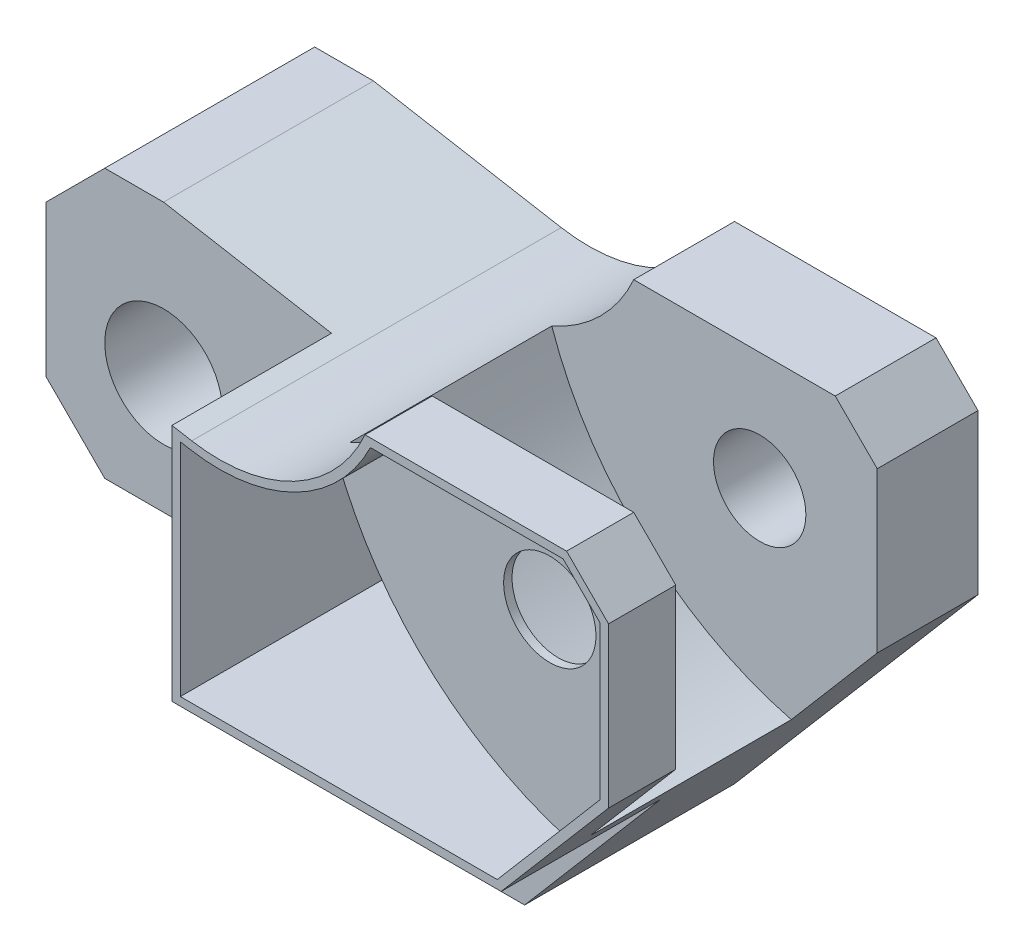
SolidWorks part; units mm, degrees
material "AISI 1020"
ref_plane "Plan de face" through (0, 0, 0) normal (0, 0, 1) x (1, 0, 0)
ref_plane "Plan de dessus" through (0, 0, 0) normal (0, 1, 0) x (1, 0, 0)
ref_plane "Plan de droite" through (0, 0, 0) normal (1, 0, 0) x (0, 0, -1)
sketch "Esquisse1" plane through (0, 0, 0) normal (0, 0, 1) x (1, 0, 0)
  line L0 (40.0103, -4.2308) -> (64.0103, -4.2308)
  line L1 (64.0103, -4.2308) -> (69.0103, -9.2308)
  line L2 (69.0103, -9.2308) -> (69.0103, -28.2308)
  line L3 (69.0103, -28.2308) -> (40.0103, -62.2308)
  line L4 (40.0103, -62.2308) -> (34.3073, -62.2308)
  line L6 (22.5858, -43.2308) -> (-9.9897, -43.2308)
  line L7 (-9.9897, -43.2308) -> (-16.9897, -36.2308)
  line L8 (-16.9897, -36.2308) -> (-16.9897, -18.2308)
  line L9 (-16.9897, -18.2308) -> (-9.9897, -11.2308)
  line L12 (-9.9897, -11.2308) -> (-2.9897, -11.2308)
  line L18 (-2.9897, -11.2308) -> (19.3717, -15.1737)
  arc A1 (27.5315, -47.4955) -> (22.5858, -43.2308) centre (22.5858, -48.2308) ccw
  arc A2 (40.0103, -4.2308) -> (19.3717, -15.1737) centre (22.671, 3.5376) cw
  arc A3 (34.3073, -62.2308) -> (27.5315, -47.4955) centre (56.2162, -43.2308) cw
  circle A4 centre (-2.9897, -29.2308) radius 7
  point P17 (24.1901, -43.2308)
  dimension "D15" = 5
  dimension "D17" = 29
  dimension "D1" = 29
  dimension "D2" = 24
  dimension "D3" = 58
  dimension "D4" = 5
  dimension "D5" = 7
  dimension "D6" = 32
  dimension "D7" = 7
  dimension "D8" = 19
  dimension "D10" = 135
  dimension "D11" = 86
  dimension "D13" = 135
  dimension "D12" = 14
  dimension "D14" = 29
  dimension "D16" = 190
  dimension "D18" = 14
  dimension "D19" = 14
  dimension "D20" = 135
  dimension "D9" = 19
  dimension "D21" = 19
extrude "Boss.-Extru.2" add sketch "Esquisse1" along normal blind 44
sketch "Esquisse2" plane through (0, 0, 44) normal (0, 0, 1) x (1, 0, 0)
  line L0 (17.0103, -43.2308) -> (17.0103, -14.7574)
  line L1 (-9.9897, -43.2308) -> (22.5858, -43.2308) construction
  line L2 (19.3717, -15.1737) -> (-2.9897, -11.2308) construction
  line L3 (56.2162, -43.2308) -> (40.0103, -62.2308)
  line L4 (69.0103, -28.2308) -> (69.0103, -9.2308) construction
  line L5 (22.5858, -43.2308) -> (56.2162, -43.2308)
  line L6 (40.0103, -62.2308) -> (69.0103, -28.2308) construction
  line L7 (40.0103, -62.2308) -> (34.3073, -62.2308)
  line L8 (17.0103, -14.7574) -> (-2.9897, -11.2308)
  line L9 (-2.9897, -11.2308) -> (-9.9897, -11.2308)
  line L10 (-9.9897, -11.2308) -> (-16.9897, -18.2308)
  line L11 (-16.9897, -18.2308) -> (-16.9897, -36.2308)
  line L12 (-16.9897, -36.2308) -> (-9.9897, -43.2308)
  line L13 (-9.9897, -43.2308) -> (17.0103, -43.2308)
  line L15 (22.5858, -43.2308) -> (23.0527, -46.7092)
  line L16 (23.0527, -46.7092) -> (29.1462, -61.7851)
  line L17 (29.1462, -61.7851) -> (34.3073, -62.2308)
  arc A0 (34.3073, -62.2308) -> (27.4847, -47.1684) centre (56.2162, -43.2308) cw
  line M10 (19.3717, -15.1737) -> (-2.9897, -11.2308)
  line M11 (-2.9897, -11.2308) -> (-9.9897, -11.2308)
  line M12 (-9.9897, -11.2308) -> (-16.9897, -18.2308)
  line M13 (-16.9897, -18.2308) -> (-16.9897, -36.2308)
  line M14 (-16.9897, -36.2308) -> (-9.9897, -43.2308)
  line M15 (-9.9897, -43.2308) -> (22.5858, -43.2308)
  arc M16 (22.5858, -43.2308) -> (27.5315, -47.4955) centre (22.5858, -48.2308) cw
  arc M17 (27.5315, -47.4955) -> (34.3073, -62.2308) centre (56.2162, -43.2308) ccw
  line M18 (34.3073, -62.2308) -> (40.0103, -62.2308)
  line M19 (40.0103, -62.2308) -> (69.0103, -28.2308)
  circle M23 centre (-2.9897, -29.2308) radius 7
  dimension "D1" = 52
extrude "Enlèv. mat.-Extru.1" cut sketch "Esquisse2" against normal blind 19 contours L0 M15 M10 M11 M12 M13 M14 M23 region at (3.5103, -42.7639, 44)
extrude "Enlèv. mat.-Extru.2" cut sketch "Esquisse2<4>" against normal blind 19 contours L5 M16 M17 M18 M19 region at (39.1003, -50.6947, 44)
sketch "Esquisse2<4>" plane through (0, 0, 44) normal (0, 0, 1) x (1, 0, 0) same geometry as "Esquisse2"
sketch "Esquisse3" plane through (0, 0, 44) normal (0, 0, 1) x (1, 0, 0)
  line L0 (64.0103, -4.2308) -> (40.0103, -4.2308) construction
  line L2 (69.0103, -28.2308) -> (69.0103, -9.2308) construction
  circle A0 centre (55.0103, -18.2308) radius 5.5
  point P6 (45.2144, -20.2124)
  dimension "D1" = 14
  dimension "D2" = 14
extrude "Enlèv. mat.-Extru.3" cut sketch "Esquisse3" against normal through all contours A0
sketch "Esquisse4" plane through (0, -4.2308, 0) normal (0, 1, 0) x (1, 0, 0)
  line L0 (40.0103, -12) -> (63.6421, -12)
  line L1 (40.0103, -44) -> (40.0103, 0) construction
  line L2 (40.0103, -36) -> (64.3668, -36)
  line L3 (64.0103, 0) -> (40.0103, 0) construction
  dimension "D1" = 24
  dimension "D2" = 12
sketch "Esquisse5" plane through (69.0103, 0, 0) normal (1, 0, 0) x (0, 0, -1)
  line L1 (-36, -40.3011) -> (-12, -40.3011)
  line L2 (-12, -40.3011) -> (-12, -4.2308)
  line L3 (-44, -4.2308) -> (0, -4.2308) construction
  line L5 (0, -9.2308) -> (0, -4.2308) construction
  line L6 (-36, -4.3011) -> (-36, 0.6989)
  line L7 (-36, 0.6989) -> (-12, 0.6989)
  line L8 (-12, 0.6989) -> (-12, -4.2308)
  dimension "D1" = 36
  dimension "D2" = 24
  dimension "D3" = 12
  dimension "D4" = 41
ref_plane "Plan18" through (0, 0, 12) normal (0, 0, -1) x (-1, 0, 0)
sketch "Esquisse8" plane through (0, 0, 12) normal (0, 0, -1) x (-1, 0, 0)
  line L0 (-69.0103, -40.3011) -> (-69.0103, -4.2308) construction
  line L15 (-40.0103, -4.2308) -> (-64.0103, -4.2308)
  line L16 (-64.0103, -4.2308) -> (-69.0103, -9.2308)
  line L17 (-69.0103, -9.2308) -> (-69.0103, -28.2308)
  line L18 (-69.0103, -28.2308) -> (-40.0103, -62.2308)
  line L19 (-40.0103, -62.2308) -> (-34.3073, -62.2308)
  line L20 (-22.5858, -43.2308) -> (9.9897, -43.2308)
  line L21 (9.9897, -43.2308) -> (16.9897, -36.2308)
  line L22 (16.9897, -36.2308) -> (16.9897, -18.2308)
  line L23 (16.9897, -18.2308) -> (9.9897, -11.2308)
  line L24 (9.9897, -11.2308) -> (2.9897, -11.2308)
  line L25 (2.9897, -11.2308) -> (-19.3717, -15.1737)
  line L26 (-40.0103, -4.2308) -> (-64.0103, -4.2308)
  line L27 (-64.0103, -4.2308) -> (-69.0103, -9.2308)
  line L28 (-69.0103, -9.2308) -> (-69.0103, -28.2308)
  line L29 (-69.0103, -28.2308) -> (-40.0103, -62.2308)
  line L30 (-40.0103, -62.2308) -> (-34.3073, -62.2308)
  line L31 (-22.5858, -43.2308) -> (9.9897, -43.2308)
  line L32 (9.9897, -43.2308) -> (16.9897, -36.2308)
  line L33 (16.9897, -36.2308) -> (16.9897, -18.2308)
  line L34 (16.9897, -18.2308) -> (9.9897, -11.2308)
  line L35 (9.9897, -11.2308) -> (2.9897, -11.2308)
  line L36 (2.9897, -11.2308) -> (-19.3717, -15.1737)
  circle A0 centre (-69.0103, -0.5289) radius 41
  arc A4 (-40.0103, -4.2308) -> (-19.3717, -15.1737) centre (-22.671, 3.5376) ccw
  arc A5 (-34.3073, -62.2308) -> (-27.5315, -47.4955) centre (-56.2162, -43.2308) ccw
  arc A6 (-22.5858, -43.2308) -> (-27.5315, -47.4955) centre (-22.5858, -48.2308) ccw
  arc A7 (-40.0103, -4.2308) -> (-19.3717, -15.1737) centre (-22.671, 3.5376) ccw
  arc A8 (-34.3073, -62.2308) -> (-27.5315, -47.4955) centre (-56.2162, -43.2308) ccw
  arc A9 (-22.5858, -43.2308) -> (-27.5315, -47.4955) centre (-22.5858, -48.2308) ccw
  point P4 (0, 0)
  point P6 (-58.775, -40.2308)
  dimension "D1" = 0
  dimension "D2" = 36
extrude "Enlèv. mat.-Extru.21" cut sketch "Esquisse8" against normal blind 24 contours A7 L26 L27 L28 L29 A0 region at (52.1987, -19.7995, 12)
sketch "Esquisse9" plane through (0, 0, 44) normal (0, 0, 1) x (1, 0, 0)
  line L0 (18.0103, -42.2308) -> (55.7548, -42.2308)
  line L1 (55.7548, -42.2308) -> (68.0103, -27.8623)
  line L2 (68.0103, -27.8623) -> (68.0103, -9.645)
  line L3 (68.0103, -9.645) -> (63.5961, -5.2308)
  line L4 (63.5961, -5.2308) -> (40.6464, -5.2308)
  line L5 (19.198, -16.1585) -> (18.0103, -15.9491)
  line L6 (18.0103, -15.9491) -> (18.0103, -42.2308)
  line L7 (17.0103, -43.2308) -> (56.2162, -43.2308)
  line L8 (56.2162, -43.2308) -> (69.0103, -28.2308)
  line L9 (69.0103, -28.2308) -> (69.0103, -9.2308)
  line L10 (69.0103, -9.2308) -> (64.0103, -4.2308)
  line L11 (64.0103, -4.2308) -> (40.0103, -4.2308)
  line L12 (19.3717, -15.1737) -> (17.0103, -14.7574)
  line L13 (17.0103, -14.7574) -> (17.0103, -43.2308)
  line L14 (17.0103, -43.2308) -> (56.2162, -43.2308)
  line L15 (56.2162, -43.2308) -> (69.0103, -28.2308)
  line L16 (69.0103, -28.2308) -> (69.0103, -9.2308)
  line L17 (69.0103, -9.2308) -> (64.0103, -4.2308)
  line L18 (64.0103, -4.2308) -> (40.0103, -4.2308)
  line L19 (19.3717, -15.1737) -> (17.0103, -14.7574)
  line L20 (17.0103, -14.7574) -> (17.0103, -43.2308)
  arc A0 (19.198, -16.1585) -> (40.6464, -5.2308) centre (22.671, 3.5376) ccw
  arc A1 (19.3717, -15.1737) -> (40.0103, -4.2308) centre (22.671, 3.5376) ccw
  arc A2 (19.3717, -15.1737) -> (40.0103, -4.2308) centre (22.671, 3.5376) ccw
  dimension "D1" = 0
  dimension "D2" = 1
extrude "Enlèv. mat.-Extru.22" cut sketch "Esquisse9" against normal offset from surface (7 mm away) 1 contours L0 L1 L2 L3 L4 A0 L5 L6 up to face at (54.775, -17.4241, 36)
ref_plane "Plan19" through (58.775, -40.2308, 36) normal (-0.9683, 0.2496, 0) x (0, 0, 1)
sketch "Esquisse11" plane through (0, 0, 37) normal (0, 0, 1) x (1, 0, 0)
  line L4 (56.2162, -43.2308) -> (69.0103, -28.2308) construction
  line L8 (17.0103, -43.2308) -> (56.2162, -43.2308) construction
  line L9 (17.0103, -43.2308) -> (17.0103, -14.7574) construction
  line L10 (19.3717, -15.1737) -> (17.0103, -14.7574) construction
  line L11 (56.2162, -43.2308) -> (58.775, -40.2308)
  line L12 (17.0103, -43.2308) -> (56.2162, -43.2308)
  line L13 (17.0103, -43.2308) -> (17.0103, -14.7574)
  line L14 (19.3717, -15.1737) -> (17.0103, -14.7574)
  line L15 (55.7548, -42.2308) -> (56.9972, -40.7742)
  line L16 (18.0103, -42.2308) -> (55.7548, -42.2308)
  line L17 (18.0103, -42.2308) -> (18.0103, -15.9491)
  line L18 (19.198, -16.1585) -> (18.0103, -15.9491)
  arc A0 (30.2472, -13.8865) -> (58.775, -40.2308) centre (69.0103, -0.5289) ccw construction
  arc A1 (30.2472, -13.8865) -> (57.7083, -39.9404) centre (69.0103, -0.5289) ccw
  arc A3 (19.3717, -15.1737) -> (40.0103, -4.2308) centre (22.671, 3.5376) ccw construction
  arc A4 (19.3717, -15.1737) -> (30.2472, -13.8865) centre (22.671, 3.5376) ccw
  arc A5 (30.2472, -13.8865) -> (58.775, -40.2308) centre (69.0103, -0.5289) ccw
  arc A6 (29.657, -15.2026) -> (56.9972, -40.7742) centre (69.0103, -0.5289) ccw
  arc A7 (19.198, -16.1585) -> (29.657, -15.2026) centre (22.671, 3.5376) ccw
  dimension "D1" = 1
extrude "Enlèv. mat.-Extru.23" cut sketch "Esquisse11" against normal offset from surface (25 mm away) 12 contours A6 L15 L16 L17 L18 A7 up to face at (60.5103, -18.2308, 0)
equation "\"A\" = 86"
equation "\"B\" = 58"
equation "\"C\" = 44"
equation "\"D11@Esquisse1\"=\"A\""
equation "\"D3@Esquisse1\"=\"B\""
equation "\"D1@Boss.-Extru.2\"=\"C\""
